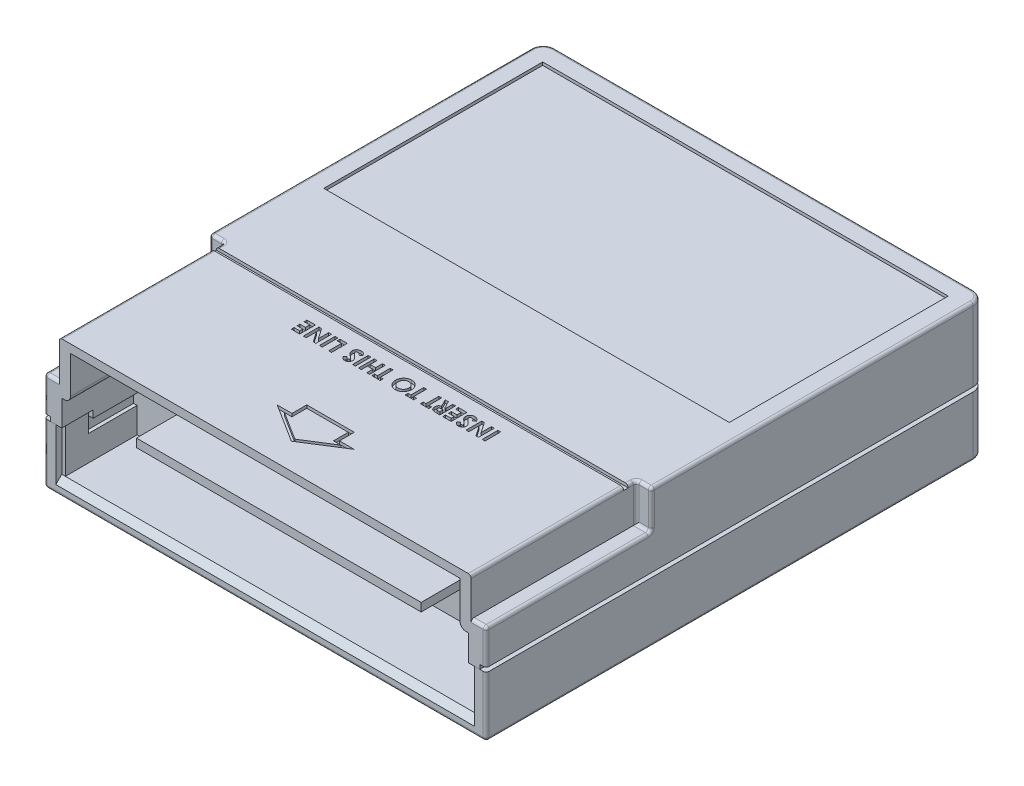
SolidWorks part; units mm, degrees
other "PCB"
other "Back"
other "Front"
ref_plane "Front Plane" through (0, 0, 0) normal (0, 0, 1) x (1, 0, 0)
ref_plane "Top Plane" through (0, 0, 0) normal (0, 1, 0) x (1, 0, 0)
ref_plane "Right Plane" through (0, 0, 0) normal (1, 0, 0) x (0, 0, -1)
sketch "Sketch1" plane through (0, 0, 0) normal (0, 1, 0) x (1, 0, 0)
  line L0 (0, 0) -> (0, 65.8) construction
  line L1 (-23.975, 0) -> (-23.975, 21.47)
  line L2 (-23.975, 21.47) -> (-26.93, 21.47)
  line L3 (-26.93, 21.47) -> (-26.93, 65.8)
  line L4 (-26.93, 65.8) -> (26.93, 65.8)
  line L5 (26.93, 65.8) -> (26.93, 21.47)
  line L6 (26.93, 21.47) -> (23.975, 21.47)
  line L7 (23.975, 21.47) -> (23.975, 0)
  line L8 (23.975, 0) -> (-23.975, 0)
  line L9 (-20.025, 17.13) -> (20.025, 17.13) construction
  circle A0 centre (-20.025, 19.03) radius 1.9
  circle A1 centre (0, 19.03) radius 2.65
  circle A2 centre (20.025, 19.03) radius 1.9
  point P16 (0, 0)
  dimension "D5" = 3.8
  dimension "D8" = 5.3
  dimension "D1" = 53.86
  dimension "D2" = 44.33
  dimension "D3" = 65.8
  dimension "D4" = 47.95
  dimension "D6" = 36.25
  dimension "D7" = 17.13
extrude "Boss-Extrude1" add sketch "Sketch1" along normal mid plane 1.6
sketch "Sketch2" plane through (0, 0.8, 0) normal (0, 1, 0) x (1, 0, 0)
  line L0 (0, 0) -> (0, 65.8) construction
  line L1 (-26.125, 39.52) -> (26.125, 39.52)
  line L2 (-26.125, 39.52) -> (-26.125, 25.82)
  line L3 (-26.125, 25.82) -> (26.125, 25.82)
  line L4 (26.125, 39.52) -> (26.125, 25.82)
  line L5 (26.93, 65.8) -> (-26.93, 65.8) construction
  line L6 (-23.975, 0) -> (23.975, 0) construction
  dimension "D1" = 52.25
  dimension "D2" = 13.7
  dimension "D3" = 25.82
extrude "Boss-Extrude2" add sketch "Sketch2" along normal blind 4.4
sketch "Sketch3" plane through (0, 0.8, 0) normal (0, 1, 0) x (1, 0, 0)
  line L0 (26.93, 21.47) -> (26.93, 65.8) construction
  line L1 (11.66, 63.46) -> (22.66, 63.46)
  line L2 (11.66, 63.46) -> (11.66, 42.86)
  line L3 (11.66, 42.86) -> (22.66, 42.86)
  line L4 (22.66, 63.46) -> (22.66, 42.86)
  line L5 (26.93, 65.8) -> (-26.93, 65.8) construction
  dimension "D1" = 20.6
  dimension "D2" = 11
  dimension "D3" = 4.27
  dimension "D4" = 2.34
extrude "Boss-Extrude3" add sketch "Sketch3" along normal blind 2.88
sketch "Sketch4" plane through (0, 0.8, 0) normal (0, 1, 0) x (1, 0, 0)
  line L0 (26.93, 65.8) -> (-26.93, 65.8) construction
  line L1 (0, 54.1) -> (0, 19.03) construction
  circle A0 centre (0, 54.1) radius 1.6
  dimension "D1" = 3.2
  dimension "D2" = 10.1
extrude "Boss-Extrude4" add sketch "Sketch4" along normal blind 6.75
sketch "Sketch5" plane through (0, 0.8, 0) normal (0, 1, 0) x (1, 0, 0)
  line L0 (23.975, 0) -> (23.975, 21.47) construction
  line L1 (-23.975, 0) -> (23.975, 0)
  line L2 (-23.975, 0) -> (-23.975, 8.52)
  line L3 (-23.975, 8.52) -> (23.975, 8.52)
  line L4 (23.975, 0) -> (23.975, 8.52)
  dimension "D1" = 8.52
extrude "Cut-Extrude1" cut sketch "Sketch5" against normal blind 0.1
mirror "Mirror1" about plane through (0, 0, 0) normal (0, 1, 0) of "Cut-Extrude1"
ref_plane "Plane1" through (0, -4.72, 0) normal (0, -1, 0) x (-1, 0, 0)
sketch "Sketch6" plane through (0, -4.72, 0) normal (0, -1, 0) x (-1, 0, 0)
  line L0 (0, 19.03) -> (0, 38.8) construction
  line L1 (-11.845, 38.8) -> (11.845, 38.8)
  line L2 (-11.845, 38.8) -> (-11.845, 80.73)
  line L3 (-11.845, 80.73) -> (11.845, 80.73)
  line L4 (11.845, 38.8) -> (11.845, 80.73)
  line L5 (23.975, 0) -> (-23.975, 0) construction
  dimension "D1" = 41.93
  dimension "D2" = 23.69
  dimension "D3" = 38.8
extrude "Boss-Extrude5" add sketch "Sketch6" along normal blind 1.09 separate body
sketch "Sketch7" plane through (0, -4.72, 0) normal (0, 1, 0) x (1, 0, 0)
  line L0 (0, 80.73) -> (0, 47.8) construction
  line L1 (-7.5, 47.8) -> (7.5, 47.8)
  line L2 (-7.5, 47.8) -> (-7.5, 43.8)
  line L3 (-7.5, 43.8) -> (7.5, 43.8)
  line L4 (7.5, 47.8) -> (7.5, 43.8)
  line L5 (-11.845, 80.73) -> (11.845, 80.73) construction
  line L6 (11.845, 38.8) -> (-11.845, 38.8) construction
  dimension "D1" = 15
  dimension "D2" = 4
  dimension "D3" = 5
extrude "Boss-Extrude6" add sketch "Sketch7" along normal up to next
sketch "Sketch8" plane through (0, -4.72, 0) normal (0, 1, 0) x (1, 0, 0)
  line L0 (-5, 80.73) -> (-3.795, 79.37)
  line L1 (-11.845, 80.73) -> (11.845, 80.73) construction
  line L2 (-3.795, 79.37) -> (3.795, 79.37)
  line L3 (3.795, 79.37) -> (5, 80.73)
  line L4 (5, 80.73) -> (-5, 80.73)
  line L5 (0, 79.37) -> (0, 65.8) construction
  line L6 (26.93, 65.8) -> (-26.93, 65.8) construction
  dimension "D1" = 7.59
  dimension "D2" = 1.36
  dimension "D3" = 10
extrude "Cut-Extrude2" cut sketch "Sketch8" against normal through all both and the other way through all
sketch "Sketch9" plane through (0, -4.72, 0) normal (0, 1, 0) x (1, 0, 0)
  line L0 (0, 79.37) -> (0, 77.88) construction
  line L1 (-7.5, 77.88) -> (7.5, 77.88)
  line L2 (-7.5, 77.88) -> (-7.5, 62.13)
  line L3 (-7.5, 62.13) -> (7.5, 62.13)
  line L4 (7.5, 77.88) -> (7.5, 62.13)
  line L5 (-3.795, 79.37) -> (3.795, 79.37) construction
  line L6 (-11.845, 80.73) -> (-5, 80.73) construction
  dimension "D1" = 15
  dimension "D2" = 2.85
  dimension "D3" = 15.75
extrude "Boss-Extrude7" add sketch "Sketch9" along normal blind 1.95
sketch "Sketch10" plane through (0, 0.8, 0) normal (0, 1, 0) x (1, 0, 0)
  circle A0 centre (-20.025, 19.03) radius 1.73
  circle A1 centre (0, 19.03) radius 2.47
  circle A2 centre (20.025, 19.03) radius 1.73
  circle A3 centre (0, 19.03) radius 1.515
  dimension "D1" = 3.46
  dimension "D2" = 4.94
  dimension "D3" = 3.03
extrude "Boss-Extrude8" add sketch "Sketch10" against normal up to surface (1.6 mm away) separate body up to face at (0, -0.8, -16.38)
sketch "Sketch11" plane through (0, -0.8, 0) normal (0, -1, 0) x (1, 0, 0)
  circle A0 centre (20.025, -19.03) radius 2.5
  circle A1 centre (-20.025, -19.03) radius 2.5
  circle A2 centre (0, -19.03) radius 1.515
  circle A3 centre (0, -19.03) radius 3.28
  circle A4 centre (0, -19.03) radius 1.515 construction
  dimension "D1" = 5
  dimension "D2" = 6.56
extrude "Boss-Extrude9" add sketch "Sketch11" along normal blind 8.79 separate body
sketch "Sketch12" plane through (0, -9.59, 0) normal (0, -1, 0) x (1, 0, 0)
  circle A0 centre (0, -19.03) radius 1.515
  circle A1 centre (0, -19.03) radius 4.625
  circle A2 centre (0, -19.03) radius 1.515 construction
  dimension "D1" = 9.25
extrude "Boss-Extrude10" add sketch "Sketch12" against normal blind 2.3 separate body
sketch "Sketch13" plane through (0, -9.59, 0) normal (0, -1, 0) x (1, 0, 0)
  line L0 (-37.215, 2.285) -> (37.215, 2.285)
  line L1 (37.215, 2.285) -> (37.215, -81.73)
  line L2 (37.215, -81.73) -> (-37.215, -81.73)
  line L3 (-37.215, -81.73) -> (-37.215, 2.285)
  line L4 (0, 0) -> (0, 2.285) construction
  line L5 (-11.845, -80.73) -> (-5, -80.73) construction
  circle A0 centre (0, -19.03) radius 1.515 construction
  circle A1 centre (0, -19.03) radius 1.515 construction
  circle A2 centre (0, -19.03) radius 1.515
  dimension "D3" = 19.8
  dimension "D1" = 74.43
  dimension "D2" = 1
extrude "Boss-Extrude11" add sketch "Sketch13" along normal blind 2.35 separate body
fillet "Fillet1" radius 2 2 edges at (37.215, -10.765, -81.73) (-37.215, -10.765, -81.73)
sketch "Sketch14" plane through (0, -9.59, 0) normal (0, 1, 0) x (1, 0, 0)
  line L0 (-35.265, -2.285) -> (-35.265, 77.43)
  line L1 (-33.265, 79.43) -> (33.265, 79.43)
  line L2 (35.265, 77.43) -> (35.265, -2.285)
  line L3 (35.265, -2.285) -> (37.215, -2.285)
  line L4 (37.215, -2.285) -> (37.215, 79.73)
  line L5 (35.215, 81.73) -> (-35.215, 81.73)
  line L6 (-37.215, 79.73) -> (-37.215, -2.285)
  line L7 (-37.215, -2.285) -> (37.215, -2.285)
  line L8 (37.215, -2.285) -> (37.215, 79.73)
  line L9 (35.215, 81.73) -> (-35.215, 81.73)
  line L10 (-37.215, 79.73) -> (-37.215, -2.285)
  line L11 (-37.215, -2.285) -> (-35.265, -2.285)
  arc A0 (33.265, 79.43) -> (35.265, 77.43) centre (33.265, 77.43) cw
  arc A1 (-35.265, 77.43) -> (-33.265, 79.43) centre (-33.265, 77.43) cw
  arc A2 (37.215, 79.73) -> (35.215, 81.73) centre (35.215, 79.73) ccw
  arc A3 (-35.215, 81.73) -> (-37.215, 79.73) centre (-35.215, 79.73) ccw
  arc A4 (37.215, 79.73) -> (35.215, 81.73) centre (35.215, 79.73) ccw
  arc A5 (-35.215, 81.73) -> (-37.215, 79.73) centre (-35.215, 79.73) ccw
  dimension "D5" = 2
  dimension "D2" = 1.95
  dimension "D3" = 2.3
  dimension "D4" = 1.95
  dimension "D1" = 0
extrude "Boss-Extrude12" add sketch "Sketch14" along normal blind 7.75 separate body
combine bodies "Combine1" operation type add bodies to combine 111 119 118 117 116 115 114 113 112
sketch "Sketch21" plane through (0, 0, -79.43) normal (0, 0, 1) x (1, 0, 0)
  line L0 (11.845, -5.81) -> (-11.845, -5.81) construction
  line L1 (-12.345, -2.47) -> (12.345, -2.47)
  line L2 (-12.345, -2.47) -> (-12.345, -6.06)
  line L3 (-12.345, -6.06) -> (12.345, -6.06)
  line L4 (12.345, -2.47) -> (12.345, -6.06)
  line L5 (-11.845, -5.81) -> (-11.845, -4.72) construction
  line L6 (11.845, -5.81) -> (11.845, -4.72) construction
  line L7 (-7.5, -2.77) -> (7.5, -2.77) construction
  point P4 (12.3369, -2.3754)
  dimension "D1" = 0.25
  dimension "D2" = 0.5
  dimension "D3" = 0.5
  dimension "D4" = 0.3
extrude "Cut-Extrude4" cut sketch "Sketch21" against normal blind 1.4 and the other way blind 10
chamfer "Chamfer1" distance 1 angle 45 1 edges at (0, -9.59, 2.285)
ref_plane "Plane2" through (0, 0, -10.815) normal (0, 0, 1) x (1, 0, 0)
sketch "Sketch15" plane through (0, -9.59, 0) normal (0, 1, 0) x (1, 0, 0)
  line L0 (35.265, 77.43) -> (35.265, -2.285) construction
  line L1 (-33.265, 79.43) -> (33.265, 79.43) construction
  line L2 (-35.265, -1.285) -> (-35.265, 77.43) construction
  line L3 (35.265, 77.43) -> (35.265, -1.285)
  line L4 (-33.265, 79.43) -> (33.265, 79.43)
  line L5 (-35.265, -1.285) -> (-35.265, 77.43)
  line L6 (-34.665, -1.285) -> (-34.665, 77.43)
  line L7 (-33.265, 78.83) -> (33.265, 78.83)
  line L8 (34.665, 77.43) -> (34.665, -1.285)
  line L11 (-35.265, -1.285) -> (-34.665, -1.285)
  line L12 (34.665, -1.285) -> (35.265, -1.285)
  line L13 (35.265, -2.285) -> (-35.265, -2.285) construction
  line L14 (35.265, 77.43) -> (35.265, -2.285) construction
  line L15 (34.665, 77.43) -> (34.665, -2.285) construction
  line L17 (-35.265, -1.285) -> (-35.265, 77.43) construction
  line L18 (-34.665, -1.285) -> (-34.665, 77.43) construction
  arc A0 (35.265, 77.43) -> (33.265, 79.43) centre (33.265, 77.43) ccw construction
  arc A1 (-33.265, 79.43) -> (-35.265, 77.43) centre (-33.265, 77.43) ccw construction
  arc A2 (35.265, 77.43) -> (33.265, 79.43) centre (33.265, 77.43) ccw
  arc A3 (-33.265, 79.43) -> (-35.265, 77.43) centre (-33.265, 77.43) ccw
  arc A4 (-33.265, 78.83) -> (-34.665, 77.43) centre (-33.265, 77.43) ccw
  arc A5 (34.665, 77.43) -> (33.265, 78.83) centre (33.265, 77.43) ccw
  dimension "D2" = 1
  dimension "D1" = 0.6
extrude "Boss-Extrude13" add sketch "Sketch15" along normal blind 4.3
sketch "Sketch17" plane through (0, -5.29, 0) normal (0, 1, 0) x (1, 0, 0)
  line L0 (-35.265, -2.285) -> (-35.265, 77.43) construction
  line L1 (-34.665, -1.285) -> (-35.265, -1.285)
  line L2 (-34.665, -1.285) -> (-34.665, 2.615)
  line L3 (-34.665, 2.615) -> (-35.265, 2.615)
  line L4 (-35.265, -1.285) -> (-35.265, 2.615)
  dimension "D1" = 3.9
extrude "Boss-Extrude14" add sketch "Sketch17" along normal up to surface (3.45 mm away) up to face at (0, -1.84, -52.4297)
mirror "Mirror2" about plane through (0, 0, 0) normal (1, 0, 0) of "Boss-Extrude14"
sketch "Sketch18" plane through (0, 0, -10.815) normal (0, 0, 1) x (1, 0, 0)
  line L0 (-34.665, -9.59) -> (-34.665, -5.29)
  line L1 (-34.665, -5.29) -> (-35.265, -5.29)
  line L2 (-35.265, -5.29) -> (-35.265, -3.09)
  line L3 (-35.265, -1.84) -> (-35.265, -10.59) construction
  line L4 (-35.265, -3.09) -> (-33.965, -3.09)
  line L5 (-33.965, -3.09) -> (-33.965, 1.21)
  line L6 (-33.965, 1.21) -> (-24.215, 1.21)
  line L7 (-24.215, 1.21) -> (-24.215, -1.09)
  line L8 (-24.215, -1.09) -> (24.215, -1.09)
  line L9 (24.215, -1.09) -> (24.215, 1.21)
  line L10 (24.215, 1.21) -> (33.965, 1.21)
  line L11 (33.965, 1.21) -> (33.965, -3.09)
  line L12 (33.965, -3.09) -> (35.265, -3.09)
  line L13 (35.265, -3.09) -> (35.265, -5.29)
  line L14 (35.265, -5.29) -> (34.665, -5.29)
  line L15 (34.665, -5.29) -> (34.665, -9.59)
  line L16 (34.665, -9.59) -> (-34.665, -9.59)
  line L17 (-37.215, -1.84) -> (-35.265, -1.84) construction
  line L18 (0, -9.59) -> (0, -1.09) construction
  line L19 (-37.215, -1.84) -> (-37.215, -11.94) construction
  dimension "D1" = 1.25
  dimension "D2" = 9.75
  dimension "D3" = 3.25
  dimension "D4" = 10.8
  dimension "D5" = 8.5
extrude "Boss-Extrude15" add sketch "Sketch18" against normal blind 1.7
sketch "Sketch19" plane through (0, -9.59, 0) normal (0, 1, 0) x (1, 0, 0)
  line L0 (0, 0) -> (0, 7.9552) construction
  line L1 (-34.665, 12.515) -> (34.665, 12.515) construction
  circle A0 centre (-20, 57.515) radius 3
  circle A1 centre (20, 57.515) radius 3
  dimension "D2" = 6
  dimension "D3" = 45
  dimension "D1" = 40
extrude "Boss-Extrude16" add sketch "Sketch19" along normal up to next
sketch "Sketch20" plane through (0, -11.94, 0) normal (0, -1, 0) x (1, 0, 0)
  circle A0 centre (0, -19.03) radius 2.95
  dimension "D1" = 5.9
extrude "Cut-Extrude3" cut sketch "Sketch20" against normal blind 2.45
sketch "Sketch23" plane through (0, 0, -81.73) normal (0, 0, -1) x (-1, 0, 0)
  line L0 (-7.5, -2.77) -> (-7.5, -4.72) construction
  line L1 (-8, -4.97) -> (8, -4.97)
  line L2 (-8, -4.97) -> (-8, -2.27)
  line L3 (-8, -2.27) -> (8, -2.27)
  line L4 (8, -4.97) -> (8, -2.27)
  line L5 (7.5, -2.77) -> (7.5, -4.72) construction
  line L6 (-7.5, -2.77) -> (7.5, -2.77) construction
  line L7 (3.795, -4.72) -> (-3.795, -4.72) construction
  point P4 (-8.2461, -2.6512)
  point P5 (-8.2461, -4.8944)
  dimension "D1" = 0.5
  dimension "D2" = 0.5
  dimension "D3" = 0.5
  dimension "D4" = 0.25
extrude "Cut-Extrude5" cut sketch "Sketch23" along normal through all and the other way blind 30.88
fillet "Fillet2" radius 0.5 8 edges at (-37.215, -11.94, -38.7225) (-36.6292, -11.94, -81.1442) (0, -11.94, -81.73) (36.6292, -11.94, -81.1442) (37.215, -11.94, -38.7225) (0, -11.94, 2.285) (37.215, -6.89, 2.285) (-37.215, -6.89, 2.285)
sketch "Sketch24" plane through (0, -1.84, 0) normal (0, 1, 0) x (1, 0, 0)
  line L0 (35.265, 77.43) -> (35.265, 2.615) construction
  line L1 (-33.265, 79.43) -> (33.265, 79.43) construction
  line L2 (-35.265, 2.615) -> (-35.265, 77.43) construction
  line L3 (35.265, 77.43) -> (35.265, 2.615)
  line L4 (-33.265, 79.43) -> (33.265, 79.43)
  line L5 (-35.265, 2.615) -> (-35.265, 77.43)
  line L6 (-36.145, 2.615) -> (-36.145, 77.43)
  line L7 (-33.265, 80.31) -> (33.265, 80.31)
  line L8 (36.145, 77.43) -> (36.145, 2.615)
  line L9 (-35.265, 2.615) -> (-35.265, -2.285)
  line L10 (-35.265, -2.285) -> (-36.145, -2.285)
  line L11 (-36.145, -2.285) -> (-36.145, 2.615)
  line L12 (35.265, 2.615) -> (35.265, -2.285)
  line L13 (35.265, -2.285) -> (36.145, -2.285)
  line L14 (36.145, -2.285) -> (36.145, 2.615)
  arc A0 (35.265, 77.43) -> (33.265, 79.43) centre (33.265, 77.43) ccw construction
  arc A1 (-33.265, 79.43) -> (-35.265, 77.43) centre (-33.265, 77.43) ccw construction
  arc A2 (35.265, 77.43) -> (33.265, 79.43) centre (33.265, 77.43) ccw
  arc A3 (-33.265, 79.43) -> (-35.265, 77.43) centre (-33.265, 77.43) ccw
  arc A4 (-33.265, 80.31) -> (-36.145, 77.43) centre (-33.265, 77.43) ccw
  arc A5 (36.145, 77.43) -> (33.265, 80.31) centre (33.265, 77.43) ccw
  dimension "D1" = 0.88
extrude "Boss-Extrude17" add sketch "Sketch24" along normal blind 0.72 separate body
sketch "Sketch25" plane through (0, -1.12, 0) normal (0, 1, 0) x (1, 0, 0)
  line L1 (-37.215, 79.73) -> (-37.215, -1.785) construction
  line L2 (35.215, 81.73) -> (-35.215, 81.73) construction
  line L3 (37.215, -1.785) -> (37.215, 79.73) construction
  line L5 (35.265, 77.43) -> (35.265, -2.285) construction
  line L6 (-33.265, 79.43) -> (33.265, 79.43) construction
  line L7 (-35.265, -2.285) -> (-35.265, 77.43) construction
  line L9 (-37.215, 79.73) -> (-37.215, -1.785)
  line L10 (35.215, 81.73) -> (-35.215, 81.73)
  line L11 (37.215, -1.785) -> (37.215, 79.73)
  line L13 (35.265, 77.43) -> (35.265, -2.285)
  line L14 (-33.265, 79.43) -> (33.265, 79.43)
  line L15 (-35.265, -2.285) -> (-35.265, 77.43)
  line L16 (-36.715, -2.285) -> (-35.265, -2.285) construction
  line L17 (-36.715, -2.285) -> (-35.265, -2.285)
  line L18 (35.265, -2.285) -> (36.715, -2.285) construction
  line L19 (35.265, -2.285) -> (36.715, -2.285)
  arc A0 (-35.215, 81.73) -> (-37.215, 79.73) centre (-35.215, 79.73) ccw construction
  arc A1 (37.215, 79.73) -> (35.215, 81.73) centre (35.215, 79.73) ccw construction
  arc A2 (35.265, 77.43) -> (33.265, 79.43) centre (33.265, 77.43) ccw construction
  arc A3 (-33.265, 79.43) -> (-35.265, 77.43) centre (-33.265, 77.43) ccw construction
  arc A4 (-35.215, 81.73) -> (-37.215, 79.73) centre (-35.215, 79.73) ccw
  arc A5 (37.215, 79.73) -> (35.215, 81.73) centre (35.215, 79.73) ccw
  arc A6 (35.265, 77.43) -> (33.265, 79.43) centre (33.265, 77.43) ccw
  arc A7 (-33.265, 79.43) -> (-35.265, 77.43) centre (-33.265, 77.43) ccw
  arc A8 (-37.215, -1.785) -> (-36.715, -2.285) centre (-36.715, -1.785) ccw construction
  arc A9 (-37.215, -1.785) -> (-36.715, -2.285) centre (-36.715, -1.785) ccw
  arc A10 (36.715, -2.285) -> (37.215, -1.785) centre (36.715, -1.785) ccw construction
  arc A11 (36.715, -2.285) -> (37.215, -1.785) centre (36.715, -1.785) ccw
extrude "Boss-Extrude18" add sketch "Sketch25" along normal blind 12.29 separate body
sketch "Sketch26" plane through (0, 11.17, 0) normal (0, 1, 0) x (1, 0, 0)
  line L0 (35.265, 77.43) -> (35.265, -2.285) construction
  line L1 (-33.265, 79.43) -> (33.265, 79.43) construction
  line L2 (-35.265, -2.285) -> (-35.265, 77.43) construction
  line L3 (35.265, 77.43) -> (35.265, -2.285)
  line L4 (-33.265, 79.43) -> (33.265, 79.43)
  line L5 (-35.265, -2.285) -> (-35.265, 77.43)
  line L6 (-35.265, -2.285) -> (35.265, -2.285)
  arc A0 (35.265, 77.43) -> (33.265, 79.43) centre (33.265, 77.43) ccw construction
  arc A1 (-33.265, 79.43) -> (-35.265, 77.43) centre (-33.265, 77.43) ccw construction
  arc A2 (35.265, 77.43) -> (33.265, 79.43) centre (33.265, 77.43) ccw
  arc A3 (-33.265, 79.43) -> (-35.265, 77.43) centre (-33.265, 77.43) ccw
extrude "Boss-Extrude19" add sketch "Sketch26" against normal blind 2.39 separate body
sketch "Sketch28" plane through (0, 0, 2.285) normal (0, 0, 1) x (1, 0, 0)
  line L1 (-35.265, 8.78) -> (-32.795, 8.78)
  line L2 (-35.265, 8.78) -> (-35.265, 2.52)
  line L3 (-35.265, 2.52) -> (-32.795, 2.52)
  line L4 (-32.795, 8.78) -> (-32.795, 2.52)
  line L5 (35.265, 8.78) -> (32.795, 8.78)
  line L6 (35.265, 8.78) -> (35.265, 2.52)
  line L7 (35.265, 2.52) -> (32.795, 2.52)
  line L8 (32.795, 8.78) -> (32.795, 2.52)
  dimension "D1" = 2.47
  dimension "D2" = 6.26
extrude "Boss-Extrude20" add sketch "Sketch28" against normal blind 30.88 separate body
combine bodies "Combine2" operation type add bodies to combine 134 131 133 130 129
sketch "Sketch29" plane through (0, 11.17, 0) normal (0, 1, 0) x (1, 0, 0)
  line L0 (-37.215, 79.73) -> (-37.215, -1.785) construction
  line L1 (-37.215, 25.525) -> (-34.685, 25.525)
  line L2 (-37.215, 25.525) -> (-37.215, -2.285)
  line L3 (-37.215, -2.285) -> (-34.685, -2.285)
  line L4 (-34.685, 25.525) -> (-34.685, -2.285)
  line L5 (-36.715, -2.285) -> (36.715, -2.285) construction
  line L6 (37.215, -1.785) -> (37.215, 79.73) construction
  line L7 (37.215, 25.525) -> (34.685, 25.525)
  line L8 (37.215, 25.525) -> (37.215, -2.285)
  line L9 (37.215, -2.285) -> (34.685, -2.285)
  line L10 (34.685, 25.525) -> (34.685, -2.285)
  line L11 (0, 0) -> (0, 27.6033) construction
  dimension "D1" = 2.53
  dimension "D2" = 27.81
extrude "Cut-Extrude6" cut sketch "Sketch29" against normal blind 6.42
sketch "Sketch30" plane through (0, 0, -10.815) normal (0, 0, 1) x (1, 0, 0)
  line L0 (-32.795, 8.78) -> (32.795, 8.78)
  line L1 (32.795, 8.78) -> (32.795, 2.52)
  line L2 (32.795, 2.52) -> (35.265, 2.52)
  line L3 (35.265, 2.52) -> (35.265, 1.21)
  line L4 (35.265, 2.52) -> (35.265, -1.84) construction
  line L5 (35.265, 1.21) -> (-35.265, 1.21)
  line L6 (-35.265, 8.78) -> (-35.265, -1.84) construction
  line L7 (-35.265, 1.21) -> (-35.265, 2.52)
  line L8 (-35.265, 2.52) -> (-32.795, 2.52)
  line L9 (-32.795, 2.52) -> (-32.795, 8.78)
  line L10 (-24.215, 1.21) -> (-33.965, 1.21) construction
extrude "Boss-Extrude21" add sketch "Sketch30" against normal up to surface (1.7 mm away) up to face at (0, -3.1275, -12.515)
ref_plane "Plane3" through (0, -3.07, 0) normal (0, -1, 0) x (-1, 0, 0)
sketch "Sketch31" plane through (0, -3.07, 0) normal (0, -1, 0) x (-1, 0, 0)
  line L0 (35.265, -2.285) -> (35.265, 77.43) construction
  line L1 (-33.265, 79.43) -> (33.265, 79.43) construction
  line L2 (-35.265, 77.43) -> (-35.265, -2.285) construction
  line L3 (35.265, -2.285) -> (35.265, 77.43)
  line L4 (-33.265, 79.43) -> (33.265, 79.43)
  line L5 (-35.265, 77.43) -> (-35.265, -2.285)
  line L6 (34.265, -2.285) -> (34.265, 77.43)
  line L7 (-33.265, 78.43) -> (33.265, 78.43)
  line L8 (-34.265, 77.43) -> (-34.265, -2.285)
  line L9 (-35.265, -2.285) -> (-34.265, -2.285)
  line L10 (34.265, -2.285) -> (35.265, -2.285)
  arc A0 (35.265, 77.43) -> (33.265, 79.43) centre (33.265, 77.43) ccw construction
  arc A1 (-33.265, 79.43) -> (-35.265, 77.43) centre (-33.265, 77.43) ccw construction
  arc A2 (35.265, 77.43) -> (33.265, 79.43) centre (33.265, 77.43) ccw
  arc A3 (-33.265, 79.43) -> (-35.265, 77.43) centre (-33.265, 77.43) ccw
  arc A4 (34.265, 77.43) -> (33.265, 78.43) centre (33.265, 77.43) ccw
  arc A5 (-33.265, 78.43) -> (-34.265, 77.43) centre (-33.265, 77.43) ccw
  dimension "D1" = 1
extrude "Boss-Extrude22" add sketch "Sketch31" against normal up to next
sketch "Sketch32" plane through (0, -3.07, 0) normal (0, -1, 0) x (1, 0, 0)
  line L0 (-35.265, 2.285) -> (-35.265, -77.43) construction
  line L1 (-34.265, -10.815) -> (-35.265, -10.815)
  line L2 (-34.265, -10.815) -> (-34.265, -16.815)
  line L3 (-34.265, -16.815) -> (-35.265, -16.815)
  line L4 (-35.265, -10.815) -> (-35.265, -16.815)
  line L5 (0, 0) -> (0, -20.9928) construction
  line L6 (35.265, -10.815) -> (35.265, -16.815)
  line L7 (34.265, -16.815) -> (35.265, -16.815)
  line L8 (34.265, -10.815) -> (34.265, -16.815)
  line L9 (34.265, -10.815) -> (35.265, -10.815)
  dimension "D1" = 6
extrude "Cut-Extrude7" cut sketch "Sketch32" against normal up to surface (4.28 mm away) up to face at (0, 1.21, -11.665)
sketch "Sketch33" plane through (0, 1.21, 0) normal (0, -1, 0) x (1, 0, 0)
  line L1 (-34.265, -12.515) -> (-35.265, -12.515)
  line L2 (-34.265, -12.515) -> (-34.265, -16.815)
  line L3 (-34.265, -16.815) -> (-35.265, -16.815)
  line L4 (-35.265, -12.515) -> (-35.265, -16.815)
  line L5 (34.265, -12.515) -> (35.265, -12.515)
  line L6 (34.265, -12.515) -> (34.265, -16.815)
  line L7 (34.265, -16.815) -> (35.265, -16.815)
  line L8 (35.265, -12.515) -> (35.265, -16.815)
extrude "Cut-Extrude8" cut sketch "Sketch33" against normal up to surface (1.31 mm away) up to face at (-33.53, 2.52, -20.555)
sketch "Sketch34" plane through (0, -3.07, 0) normal (0, -1, 0) x (1, 0, 0)
  line L0 (-34.265, -10.815) -> (-34.265, 2.285) construction
  line L1 (-35.265, 2.285) -> (-34.265, 2.285)
  line L2 (-35.265, 2.285) -> (-35.265, -3.015)
  line L3 (-35.265, -3.015) -> (-34.265, -3.015)
  line L4 (-34.265, 2.285) -> (-34.265, -3.015)
  line L5 (34.265, 2.285) -> (34.265, -10.815) construction
  line L6 (35.265, 2.285) -> (34.265, 2.285)
  line L7 (35.265, 2.285) -> (35.265, -3.015)
  line L8 (35.265, -3.015) -> (34.265, -3.015)
  line L9 (34.265, 2.285) -> (34.265, -3.015)
  point P14 (0, 0)
  dimension "D1" = 5.3
extrude "Cut-Extrude9" cut sketch "Sketch34" against normal up to surface (1.23 mm away) up to face at (0, -1.84, -42.3338)
fillet "Fillet3" radius 1 4 edges at (32.795, 5.65, -28.595) (32.795, 2.52, -4.265) (-32.795, 5.65, -28.595) (-32.795, 2.52, -4.265)
chamfer "Chamfer2" distance 1 angle 45 1 edges at (0, 8.78, 2.285)
sketch "Sketch35" plane through (0, 8.78, 0) normal (0, -1, 0) x (1, 0, 0)
  line L0 (0, 0) -> (0, -3.837) construction
  line L1 (33.265, -78.43) -> (-33.265, -78.43) construction
  circle A0 centre (-26, -65.43) radius 2.5
  circle A1 centre (26, -65.43) radius 2.5
  point P6 (0, 0)
  dimension "D1" = 5
  dimension "D2" = 13
  dimension "D3" = 52
extrude "Boss-Extrude23" add sketch "Sketch35" along normal up to surface (7.98 mm away) up to face at (0, 0.8, -55.7)
sketch "Sketch36" plane through (0, 8.78, 0) normal (0, -1, 0) x (1, 0, 0)
  circle A0 centre (0, -19.03) radius 1.515
  circle A1 centre (0, -19.03) radius 3.28
extrude "Boss-Extrude24" add sketch "Sketch36" along normal up to surface (7.98 mm away) up to face at (0, 0.8, -17.515)
sketch "Sketch38" plane through (0, 11.17, 0) normal (0, 1, 0) x (1, 0, 0)
  line L0 (-34.685, -2.285) -> (-34.685, 25.525) construction
  line L1 (-34.685, 24.165) -> (34.685, 24.165)
  line L2 (-34.685, 24.165) -> (-34.685, 23.395)
  line L3 (-34.685, 23.395) -> (34.685, 23.395)
  line L4 (34.685, 24.165) -> (34.685, 23.395)
  line L5 (34.685, 25.525) -> (34.685, -2.285) construction
  line L6 (-3.5, 5.715) -> (-3.5, 8.215)
  line L7 (-3.5, 8.215) -> (3.5, 8.215)
  line L8 (3.5, 8.215) -> (3.5, 5.715)
  line L9 (3.5, 5.715) -> (4.75, 5.715)
  line L10 (4.75, 5.715) -> (0, 2.715)
  line L11 (0, 2.715) -> (-4.75, 5.715)
  line L12 (-4.75, 5.715) -> (-3.5, 5.715)
  line L13 (-34.685, -2.285) -> (34.685, -2.285) construction
  line L14 (0, 0) -> (0, 8.215) construction
  line L15 (-4, 6.215) -> (-4, 8.715)
  line L16 (-4, 8.715) -> (4, 8.715)
  line L17 (4, 8.715) -> (4, 6.215)
  line L18 (4, 6.215) -> (6.478, 6.215)
  line L19 (6.478, 6.215) -> (0, 2.1236)
  line L20 (0, 2.1236) -> (-6.478, 6.215)
  line L21 (-6.478, 6.215) -> (-4, 6.215)
  line L22 (35.215, 81.73) -> (-35.215, 81.73) construction
  line L23 (34.685, 21.095) -> (-34.685, 21.095) construction
  line L24 (-34.15, 78.6) -> (34.15, 78.6)
  line L25 (-34.15, 78.6) -> (-34.15, 41.73)
  line L26 (-34.15, 41.73) -> (34.15, 41.73)
  line L27 (34.15, 78.6) -> (34.15, 41.73)
  line L28 (34.685, 25.525) -> (34.685, -2.285) construction
  text T0 "INSERT TO THIS LINE" font "Century Gothic" height in points 10
  point P35 (0, 0)
  point P36 (34.685, 21.7011)
  point P37 (-34.685, 21.8585)
  point P38 (34.685, 21.095)
  point P41 (-34.685, 21.095)
  dimension "D1" = 0.77
  dimension "D2" = 25.68
  dimension "D3" = 7
  dimension "D4" = 9.5
  dimension "D5" = 2.5
  dimension "D6" = 5.5
  dimension "D7" = 5
  dimension "D9" = 36.87
  dimension "D10" = 68.3
  dimension "D11" = 3.13
  dimension "D12" = 2.3
  dimension "D8" = 0.5
extrude "Cut-Extrude10" cut sketch "Sketch38" against normal blind 0.5
fillet "Fillet4" radius 0.5 21 edges at (-35.7, 4.75, 2.285) (35.7, 4.75, 2.285) (-37.0686, 4.75, 2.1386) (37.0686, 4.75, 2.1386) (-34.685, 11.17, -24.845) (-37.215, 4.75, -11.87) (34.685, 11.17, -24.845) (37.215, 4.75, -11.87) (-37.215, 11.17, -52.6275) (-36.6292, 11.17, -81.1442) (0, 11.17, -81.73) (36.6292, 11.17, -81.1442) (-34.685, 7.96, -25.525) (-35.95, 11.17, -25.525) (-37.215, 7.96, -25.525) (-35.95, 4.75, -25.525) (35.95, 11.17, -25.525) (34.685, 7.96, -25.525) (35.95, 4.75, -25.525) (37.215, 7.96, -25.525) (37.215, 11.17, -52.6275)
